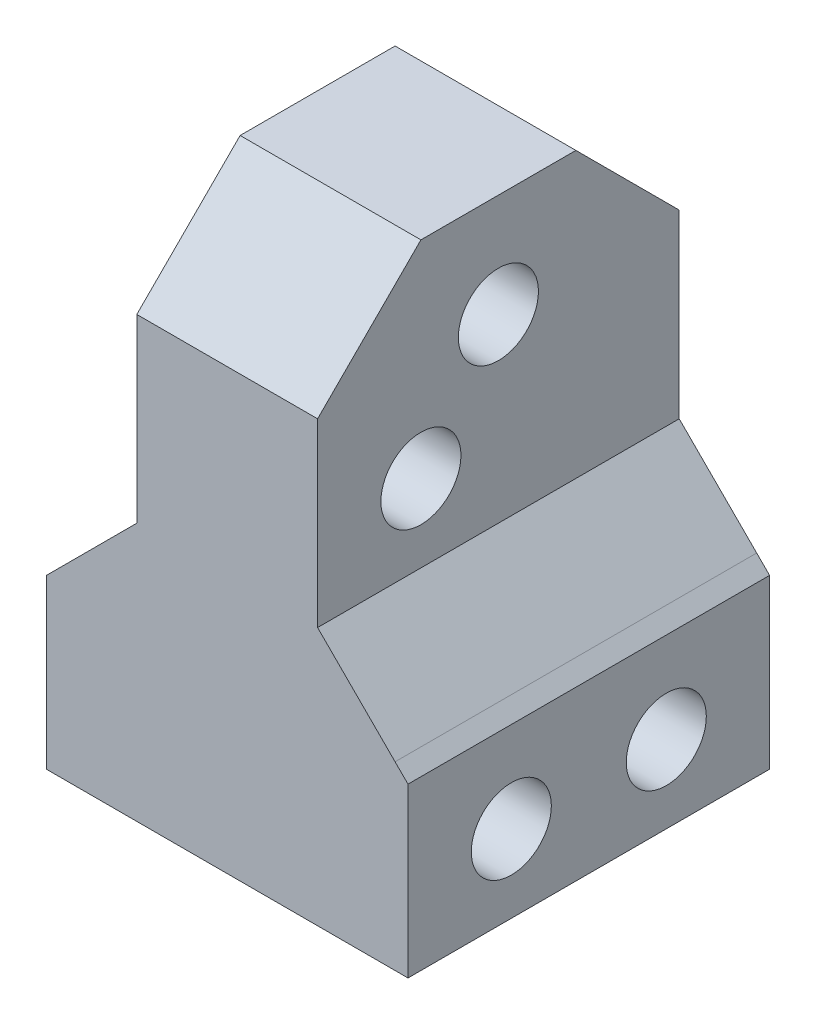
SolidWorks part; units mm, degrees
ref_plane "Front Plane" through (0, 0, 0) normal (0, 0, 1) x (1, 0, 0)
ref_plane "Top Plane" through (0, 0, 0) normal (0, 1, 0) x (1, 0, 0)
ref_plane "Right Plane" through (0, 0, 0) normal (1, 0, 0) x (0, 0, -1)
sketch "Sketch1" plane through (0, 0, 0) normal (0, 1, 0) x (1, 0, 0)
  line L1 (0, 0) -> (14, 0)
  line L2 (0, 0) -> (0, 14)
  line L3 (0, 14) -> (14, 14)
  line L4 (14, 0) -> (14, 14)
  dimension "D1" = 14
  dimension "D2" = 14
extrude "Boss-Extrude1" add sketch "Sketch1" along normal blind 7
sketch "Sketch2" plane through (0, 7, 0) normal (0, 1, 0) x (1, 0, 0)
  line L0 (7, 14) -> (7, 0) construction
  line L1 (14, 14) -> (0, 14) construction
  line L2 (0, 0) -> (14, 0) construction
  line L4 (3.5, 14) -> (10.5, 14)
  line L5 (3.5, 14) -> (3.5, 0)
  line L6 (3.5, 0) -> (10.5, 0)
  line L7 (10.5, 14) -> (10.5, 0)
  dimension "D1" = 3.5
  dimension "D2" = 3.5
extrude "Boss-Extrude2" add sketch "Sketch2" along normal blind 14
chamfer "Chamfer1" distance 3 angle 45 2 edges at (3.5, 7, -7) (10.5, 7, -7)
chamfer "Chamfer2" distance 0.5 angle 45 2 edges at (0, 7, -7) (14, 7, -7)
chamfer "Chamfer3" distance 4 angle 45 2 edges at (7, 21, -14) (7, 21, 0)
sketch "Sketch3" plane through (10.5, 0, 0) normal (1, 0, 0) x (0, 0, -1)
  line L0 (7, 21) -> (7, 10) construction
  line L1 (4, 21) -> (10, 21) construction
  line L2 (0, 10) -> (14, 10) construction
  line L3 (4, 10) -> (4, 16) construction
  line L4 (0, 17) -> (0, 10) construction
  line L5 (0, 0) -> (14, 0) construction
  line L6 (14, 6.5) -> (14, 0) construction
  circle A0 centre (7, 17) radius 1.55
  circle A1 centre (4, 13) radius 1.55
  circle A2 centre (4, 3) radius 1.55
  circle A3 centre (10, 3) radius 1.55
  dimension "D1" = 3.1
  dimension "D4" = 3.1
  dimension "D6" = 3.1
  dimension "D2" = 4
  dimension "D3" = 4
  dimension "D5" = 3
  dimension "D7" = 3
  dimension "D8" = 4
extrude "Cut-Extrude1" cut sketch "Sketch3" against normal through all both and the other way through all
sketch "Sketch5" plane through (0, 0, 0) normal (0, -1, 0) x (1, 0, 0)
  line L0 (0, -7) -> (0.7508, -7) construction
  line L1 (3.8, -0.5) -> (10.2, -0.5)
  line L2 (3.8, -0.5) -> (3.8, -13.5)
  line L3 (3.8, -13.5) -> (10.2, -13.5)
  line L4 (10.2, -0.5) -> (10.2, -13.5)
  line L5 (0, -14) -> (0, 0) construction
  line L6 (7, -14) -> (7, -16.4037) construction
  line L7 (14, -14) -> (0, -14) construction
  point P8 (3.8, -7)
  point P13 (7, -13.5)
  dimension "D1" = 6.4
  dimension "D2" = 13
  dimension "D3" = 0
  dimension "D4" = 0
extrude "Cut-Extrude2" cut sketch "Sketch5" against normal blind 0.54
